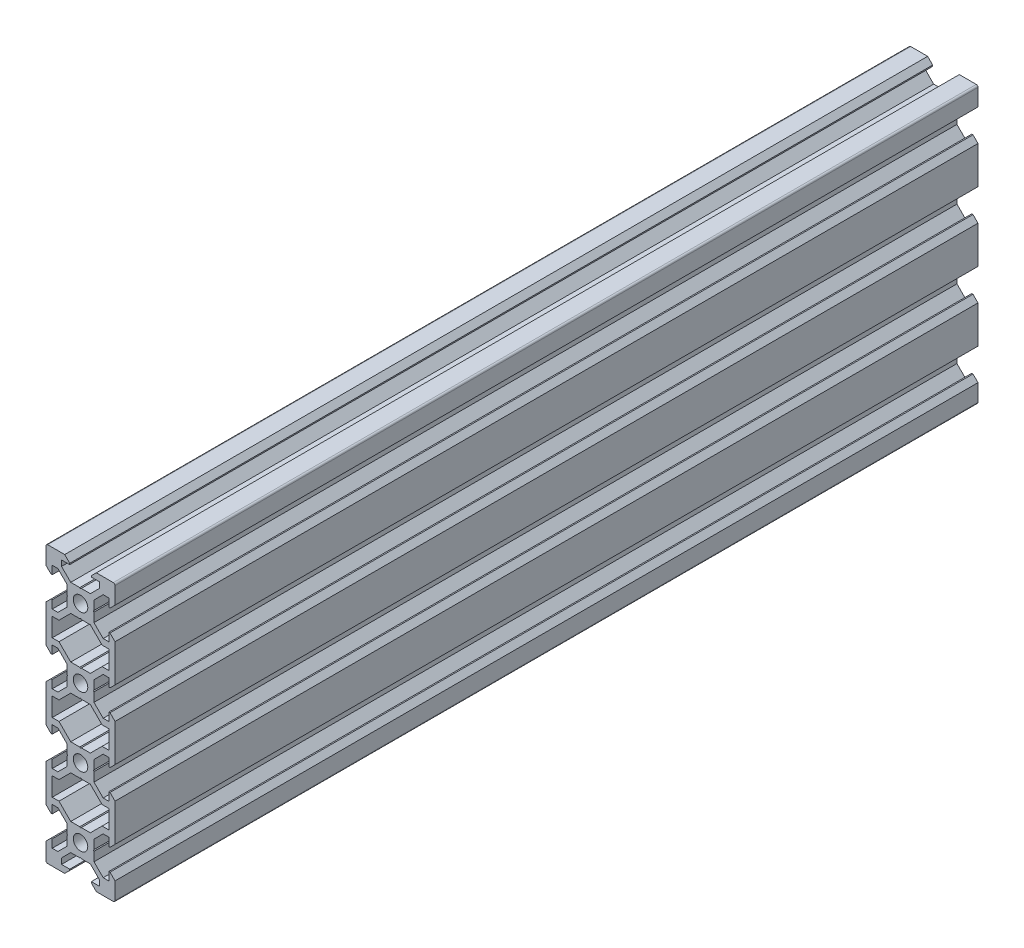
SolidWorks part; units mm, degrees
ref_plane "Plan de face" through (0, 0, 0) normal (0, 0, 1) x (1, 0, 0)
ref_plane "Plan de dessus" through (0, 0, 0) normal (0, 1, 0) x (1, 0, 0)
ref_plane "Plan de droite" through (0, 0, 0) normal (1, 0, 0) x (0, 0, -1)
ref_axis "Axe" through (0, 0, -13.782) along (0, 0, 1)
sketch "Esquisse1" plane through (0, 0, 0) normal (0, 0, 1) x (1, 0, 0)
  line L0 (0, 27.6392) -> (0, -27.6392) construction
  line L1 (-33.6074, 0) -> (33.6074, 0) construction
  line L2 (0, 0) -> (-22.2114, 22.2114) construction
  line L3 (-9.5, 10) -> (-4.58, 10)
  line L4 (-4.58, 10) -> (-3.125, 8.545)
  line L5 (-3.125, 8.545) -> (-3.125, 8.2)
  line L6 (-3.125, 8.2) -> (-5.5, 8.2)
  line L7 (-2.8393, 3.9) -> (-5.5, 6.5607)
  line L8 (-2.8393, 3.9) -> (-0.21, 3.9)
  line L9 (-5.5, 6.5607) -> (-5.5, 8.2)
  line L10 (0, 3.69) -> (0, 2.1)
  line L11 (-3.9, 2.8393) -> (-6.5607, 5.5)
  line L12 (-8.545, 3.125) -> (-8.2, 3.125)
  line L13 (-8.2, 3.125) -> (-8.2, 5.5)
  line L14 (-6.5607, 5.5) -> (-8.2, 5.5)
  line L15 (-10, 4.58) -> (-8.545, 3.125)
  line L16 (-10, 9.5) -> (-10, 4.58)
  line L17 (-0.21, 3.9) -> (0, 3.69)
  line L18 (-3.9, 2.8393) -> (-3.9, 0.21)
  line L19 (-6.2393, -12.7) -> (-8.2, -12.7)
  line L20 (-3.9, 0.21) -> (-3.69, 0)
  line L21 (-0.21, -3.9) -> (0, -3.69)
  line L22 (0, -3.69) -> (0, -2.1)
  line L23 (-6.5607, -5.5) -> (-8.2, -5.5)
  line L24 (-2.8393, -3.9) -> (-0.21, -3.9)
  line L25 (-8.545, -3.125) -> (-8.2, -3.125)
  line L26 (-10, -4.58) -> (-8.545, -3.125)
  line L27 (-8.2, -3.125) -> (-8.2, -5.5)
  line L28 (-2.8393, -3.9) -> (-6.2393, -7.3)
  line L29 (-3.9, -2.8393) -> (-6.5607, -5.5)
  line L30 (-3.9, -2.8393) -> (-3.9, -0.21)
  line L31 (-3.9, -0.21) -> (-3.69, 0)
  line L32 (-6.2393, -7.3) -> (-8.2, -7.3)
  line L33 (-8.2, -7.3) -> (-8.2, -12.7)
  line L34 (-8.2, -10) -> (-10, -10) construction
  line L35 (-10, -15.42) -> (-10, -4.58)
  line L36 (-3.9, -19.79) -> (-3.69, -20)
  line L37 (-3.9, -17.1607) -> (-3.9, -19.79)
  line L38 (-3.9, -17.1607) -> (-6.5607, -14.5)
  line L39 (-2.8393, -16.1) -> (-6.2393, -12.7)
  line L40 (-8.2, -16.875) -> (-8.2, -14.5)
  line L41 (-10, -15.42) -> (-8.545, -16.875)
  line L42 (-8.545, -16.875) -> (-8.2, -16.875)
  line L43 (-2.8393, -16.1) -> (-0.21, -16.1)
  line L44 (-6.5607, -14.5) -> (-8.2, -14.5)
  line L45 (0, -16.31) -> (0, -17.9)
  line L46 (-0.21, -16.1) -> (0, -16.31)
  line L47 (-8.2, -30) -> (-10, -30) construction
  line L48 (-3.69, -20) -> (0, -20) construction
  line L49 (-0.21, -23.9) -> (0, -23.69)
  line L50 (0, -23.69) -> (0, -22.1)
  line L51 (-6.5607, -25.5) -> (-8.2, -25.5)
  line L52 (-2.8393, -23.9) -> (-0.21, -23.9)
  line L53 (-8.545, -23.125) -> (-8.2, -23.125)
  line L54 (-10, -24.58) -> (-8.545, -23.125)
  line L55 (-8.2, -23.125) -> (-8.2, -25.5)
  line L56 (-2.8393, -23.9) -> (-6.2393, -27.3)
  line L57 (-3.9, -22.8393) -> (-6.5607, -25.5)
  line L58 (-3.9, -22.8393) -> (-3.9, -20.21)
  line L59 (-3.9, -20.21) -> (-3.69, -20)
  line L60 (-10, -24.58) -> (-10, -35.42)
  line L61 (-8.2, -32.7) -> (-8.2, -27.3)
  line L62 (-3.69, -40) -> (0, -40) construction
  line L63 (-8.2, -50) -> (-10, -50) construction
  line L64 (0, -60) -> (-22.2114, -82.2114) construction
  line L65 (-33.6074, -60) -> (33.6074, -60) construction
  line L66 (0, -87.6392) -> (0, -32.3608) construction
  line L67 (-6.2393, -32.7) -> (-8.2, -32.7)
  line L68 (-3.9, -39.79) -> (-3.69, -40)
  line L69 (-3.9, -37.1607) -> (-3.9, -39.79)
  line L70 (-3.9, -37.1607) -> (-6.5607, -34.5)
  line L71 (-2.8393, -36.1) -> (-6.2393, -32.7)
  line L72 (-8.2, -36.875) -> (-8.2, -34.5)
  line L73 (-10, -35.42) -> (-8.545, -36.875)
  line L74 (-8.545, -36.875) -> (-8.2, -36.875)
  line L75 (-6.2393, -27.3) -> (-8.2, -27.3)
  line L76 (-2.8393, -36.1) -> (-0.21, -36.1)
  line L77 (-6.5607, -34.5) -> (-8.2, -34.5)
  line L78 (0, -36.31) -> (0, -37.9)
  line L79 (-0.21, -36.1) -> (0, -36.31)
  line L80 (-0.21, -43.9) -> (0, -43.69)
  line L81 (0, -43.69) -> (0, -42.1)
  line L82 (-6.5607, -45.5) -> (-8.2, -45.5)
  line L83 (-2.8393, -43.9) -> (-0.21, -43.9)
  line L84 (-8.545, -43.125) -> (-8.2, -43.125)
  line L85 (-10, -44.58) -> (-8.545, -43.125)
  line L86 (-8.2, -43.125) -> (-8.2, -45.5)
  line L87 (-2.8393, -43.9) -> (-6.2393, -47.3)
  line L88 (-3.9, -42.8393) -> (-6.5607, -45.5)
  line L89 (-3.9, -42.8393) -> (-3.9, -40.21)
  line L90 (-3.9, -40.21) -> (-3.69, -40)
  line L91 (-10, -44.58) -> (-10, -55.42)
  line L92 (-8.2, -52.7) -> (-8.2, -47.3)
  line L93 (-6.2393, -52.7) -> (-8.2, -52.7)
  line L94 (-3.9, -59.79) -> (-3.69, -60)
  line L95 (-3.9, -57.1607) -> (-3.9, -59.79)
  line L96 (-3.9, -57.1607) -> (-6.5607, -54.5)
  line L97 (-2.8393, -56.1) -> (-6.2393, -52.7)
  line L98 (-8.2, -56.875) -> (-8.2, -54.5)
  line L99 (-10, -55.42) -> (-8.545, -56.875)
  line L100 (-8.545, -56.875) -> (-8.2, -56.875)
  line L101 (-2.8393, -56.1) -> (-0.21, -56.1)
  line L102 (-6.5607, -54.5) -> (-8.2, -54.5)
  line L103 (0, -56.31) -> (0, -57.9)
  line L104 (-0.21, -56.1) -> (0, -56.31)
  line L105 (-3.9, -60.21) -> (-3.69, -60)
  line L106 (-6.2393, -47.3) -> (-8.2, -47.3)
  line L107 (-3.9, -62.8393) -> (-3.9, -60.21)
  line L108 (-0.21, -63.9) -> (0, -63.69)
  line L109 (-10, -69.5) -> (-10, -64.58)
  line L110 (-10, -64.58) -> (-8.545, -63.125)
  line L111 (-6.5607, -65.5) -> (-8.2, -65.5)
  line L112 (-8.2, -63.125) -> (-8.2, -65.5)
  line L113 (-8.545, -63.125) -> (-8.2, -63.125)
  line L114 (-3.9, -62.8393) -> (-6.5607, -65.5)
  line L115 (0, -63.69) -> (0, -62.1)
  line L116 (-5.5, -66.5607) -> (-5.5, -68.2)
  line L117 (-2.8393, -63.9) -> (-0.21, -63.9)
  line L118 (-2.8393, -63.9) -> (-5.5, -66.5607)
  line L119 (-3.125, -68.2) -> (-5.5, -68.2)
  line L120 (-3.125, -68.545) -> (-3.125, -68.2)
  line L121 (-4.58, -70) -> (-3.125, -68.545)
  line L122 (-9.5, -70) -> (-4.58, -70)
  arc A0 (0, -2.1) -> (0, 2.1) centre (0, 0) cw
  arc A1 (-9.5, 10) -> (-10, 9.5) centre (-9.5, 9.5) ccw
  arc A2 (0, -42.1) -> (0, -37.9) centre (0, -40) cw
  arc A3 (-9.5, -70) -> (-10, -69.5) centre (-9.5, -69.5) cw
  arc A4 (0, -17.9) -> (0, -22.1) centre (0, -20) ccw
  arc A5 (0, -57.9) -> (0, -62.1) centre (0, -60) ccw
  point P4 (0, 0)
  point P7 (0, 0)
  point P30 (-10, 10)
  point P60 (0, -20)
  point P146 (-10, -70)
  dimension "D5" = 11
  dimension "D2" = 2.1
  dimension "D3" = 6.25
  dimension "D10" = 0.5
  dimension "D4" = 9.16
  dimension "D6" = 1.5
  dimension "D7" = 1.8
  dimension "D8" = 4.3
  dimension "D9" = 20
  dimension "D11" = 0.42
  dimension "D12" = 10
  dimension "D13" = 1.8
extrude "Boss.-Extru.1" add sketch "Esquisse1" along normal blind 250
sketch "Esquisse3" plane through (0, 0, 250) normal (0, 0, 1) x (1, 0, 0)
  line L0 (0, 0) -> (-9.8536, 9.8536) construction
  line L1 (-8.2, 8.2) -> (-8.2, 6.57)
  line L2 (-8.2, 6.57) -> (-7.54, 6.57)
  line L3 (-7.54, 6.57) -> (-6.57, 7.54)
  line L4 (-8.2, 3.125) -> (-8.2, 5.5) construction
  line L5 (-6.57, 8.2) -> (-6.57, 7.54)
  line L6 (-8.2, 8.2) -> (-6.57, 8.2)
  line L7 (-5.5, 6.5607) -> (-5.5, 8.2) construction
  line L8 (-10, -30) -> (6.918, -30) construction
  line L9 (-10, -24.58) -> (-10, -35.42) construction
  line L10 (-8.2, -68.2) -> (-6.57, -68.2)
  line L11 (-6.57, -68.2) -> (-6.57, -67.54)
  line L12 (-7.54, -66.57) -> (-6.57, -67.54)
  line L13 (-8.2, -66.57) -> (-7.54, -66.57)
  line L14 (-8.2, -68.2) -> (-8.2, -66.57)
  arc A0 (-9.5, 10) -> (-10, 9.5) centre (-9.5, 9.5) ccw construction
  point P13 (-7.055, 7.055)
  point P14 (-6.57, 7.87)
  point P26 (-7.055, -67.055)
  dimension "D1" = 1.07
extrude "Enlèv. mat.-Extru.1" [suppressed] cut sketch "Esquisse3" against normal through all
mirror "Symétrie1" about plane through (0, 3.69, 250) normal (-1, 0, 0) of "Enlèv. mat.-Extru.1", "Boss.-Extru.1"
